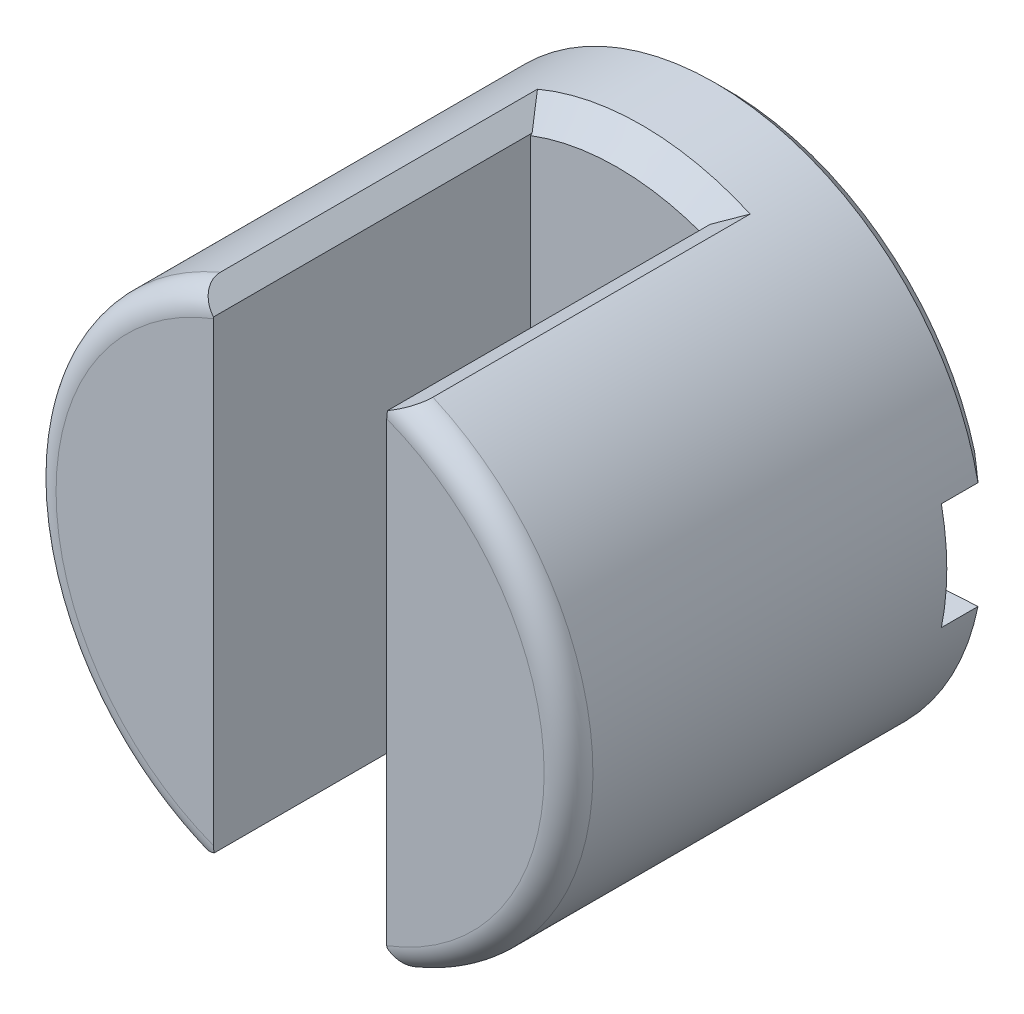
SolidWorks part; units mm, degrees
ref_plane "Front Plane" through (0, 0, 0) normal (0, 0, 1) x (1, 0, 0)
ref_plane "Top Plane" through (0, 0, 0) normal (0, 1, 0) x (1, 0, 0)
ref_plane "Right Plane" through (0, 0, 0) normal (1, 0, 0) x (0, 0, -1)
sketch "Sketch2" plane through (0, 0, 0) normal (0, 0, 1) x (1, 0, 0)
  line L0 (-3.55, 10.4114) -> (3.55, 10.4114)
  line L1 (0, 0) -> (64.1383, 0) construction
  line L2 (-3.55, 10.4114) -> (-3.55, -10.4114)
  line L3 (3.55, 10.4114) -> (3.55, -10.4114)
  line L4 (3.55, -10.4114) -> (-3.55, -10.4114)
  circle A0 centre (0, 0) radius 11
  dimension "D1" = 22
  dimension "D2" = 7.1
extrude "Pill Slot" add sketch "Sketch2" along normal blind 13 contours L3 L1 A0 | A0 L1 L2 | L1 A0 L2 | L1 L3 A0 region at (-6.638, 0, 0) region at (6.638, 4.1705, 0) region at (6.638, -4.1705, 0)
extrude "Base" add sketch "Sketch2<5>" against normal blind 4.5 contours A0
sketch "Sketch2<5>" plane through (0, 0, 0) normal (0, 0, 1) x (1, 0, 0) same geometry as "Sketch2"
sketch "Sketch3" plane through (0, 0, -4.5) normal (0, 0, -1) x (-1, 0, 0)
  line L0 (-14.1676, 1.9965) -> (-2.2271, 2.7)
  line L1 (-14.1676, -1.9965) -> (-2.2271, -2.7)
  line L2 (0, 0) -> (-16.05, 0) construction
  line L3 (0, 0) -> (0, 11.5686) construction
  line L4 (14.1676, -1.9965) -> (2.2271, -2.7)
  line L5 (14.1676, 1.9965) -> (2.2271, 2.7)
  circle A0 centre (0, 0) radius 3.5
  circle A1 centre (-14.05, 0) radius 2
  circle A2 centre (14.05, 0) radius 2
  circle A3 centre (0, 0) radius 11 construction
  circle A4 centre (0, 0) radius 11
  point P9 (0, 11.5686)
  circle M5 centre (0, 0) radius 11
  dimension "D1" = 7
  dimension "D2" = 4
  dimension "D3" = 5.4
  dimension "D4" = 16.05
  dimension "D5" = 2.7
extrude "Servo Rotation slot" cut sketch "Sketch3" against normal blind 2 contours A0 L0 L1 M5 | A0 | A0 L4 L5 M5 region at (6.8912, 0, -4.5) region at (0, 0, -4.5) region at (-6.8912, 0, -4.5)
chamfer "Chamfer1" distance 1 angle 45 4 edges at (3.55, -10.4114, 6.5) (-3.55, -10.4114, 6.5) (3.55, 10.4114, 6.5) (-3.55, 10.4114, 6.5) first distance on face at (3.55, 0, 6.5) first distance on face at (0, 0, 6.5) first distance on face at (-3.55, 0, 6.5)
fillet "Fillet1" radius 1 2 edges at (-10.9996, 0.0921, 13) (10.9996, -0.0921, 13)
chamfer "Chamfer2" distance 0.5 angle 45 8 edges at (0, 11, -4.5) (-6.5028, 2.4481, -4.5) (0, 3.5, -4.5) (6.5028, 2.4481, -4.5) (-6.5028, -2.4481, -4.5) (0, -11, -4.5) (6.5028, -2.4481, -4.5) (0, -3.5, -4.5)
chamfer "Chamfer4" distance 1 angle 45 2 edges at (0.0921, 10.9996, 0) (-0.0921, -10.9996, 0)
equation "\"D5@Sketch3\"=\"D3@Sketch3\"/2"
